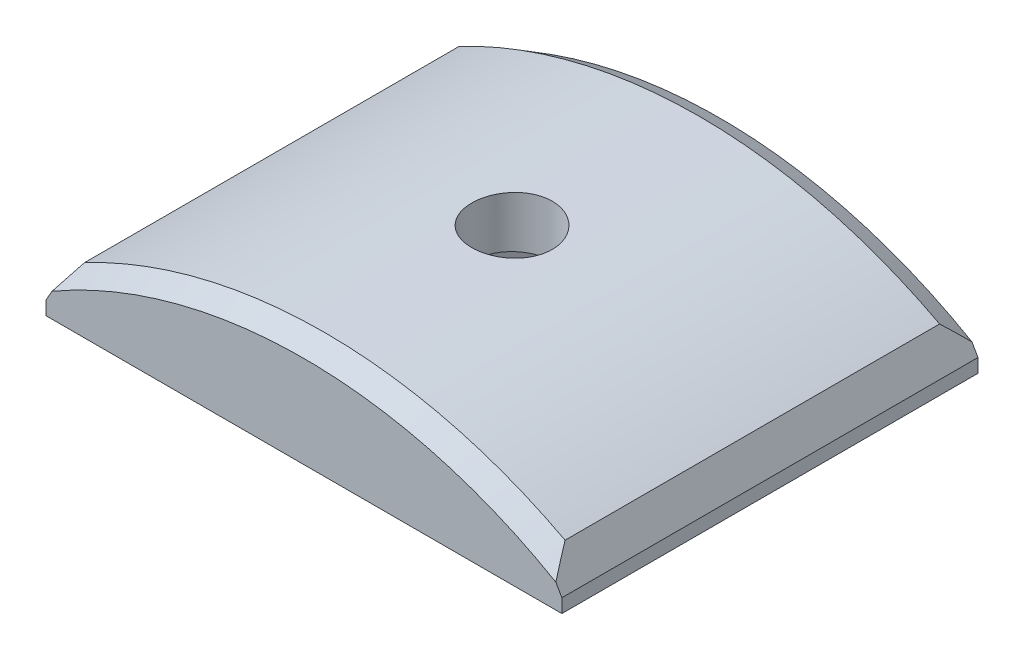
SolidWorks part; units mm, degrees
material "PET"
ref_plane "Front Plane" through (0, 0, 0) normal (0, 0, 1) x (1, 0, 0)
ref_plane "Top Plane" through (0, 0, 0) normal (0, 1, 0) x (1, 0, 0)
ref_plane "Right Plane" through (0, 0, 0) normal (1, 0, 0) x (0, 0, -1)
sketch "Sketch1" plane through (0, 0, 0) normal (0, 0, 1) x (1, 0, 0)
  line L0 (-288.86, -12.7504) -> (-326.6966, -12.7504)
  line L1 (-307.7783, -12.7504) -> (-307.7783, -6.4004) construction
  circle A0 centre (-307.7783, -37.7567) radius 31.3563 construction
  arc A1 (-288.86, -12.7504) -> (-326.6966, -12.7504) centre (-307.7783, -37.7567) ccw
  dimension "D1" = 6.35
extrude "Boss-Extrude1" add sketch "Sketch1" against normal up to surface (25.4 mm away)
sketch "Sketch2" plane through (0, 0, 0) normal (0, 0, 1) x (1, 0, 0)
  line L0 (-292.035, -12.7504) -> (-292.035, -10.6391)
  line L1 (-326.6966, -12.7504) -> (-288.86, -12.7504)
  line L2 (-292.035, -12.7504) -> (-288.86, -12.7504)
  line L3 (-307.7783, -12.7504) -> (-307.7783, -6.4004) construction
  line L4 (-326.6966, -12.7504) -> (-288.86, -12.7504) construction
  line L5 (-323.5216, -12.7504) -> (-326.6966, -12.7504)
  line L6 (-323.5216, -12.7504) -> (-323.5216, -10.6391)
  arc A0 (-288.86, -12.7504) -> (-326.6966, -12.7504) centre (-307.7783, -37.7567) ccw construction
  arc A1 (-288.86, -12.7504) -> (-326.6966, -12.7504) centre (-307.7783, -37.7567) ccw
  arc A2 (-288.86, -12.7504) -> (-292.035, -10.6391) centre (-307.7783, -37.7567) ccw
  arc A3 (-326.6966, -12.7504) -> (-323.5216, -10.6391) centre (-307.7783, -37.7567) cw
  dimension "D2" = 3.175
  dimension "D1" = 0
extrude "Cut-Extrude1" cut sketch "Sketch2" against normal up to next
hole_wizard "#8 Clearance Hole1" positions "Sketch3" profile "Sketch4" hole size "#8" standard "ANSI Inch" end condition through all
sketch "Sketch3" plane through (0, -12.7504, 0) normal (0, -1, 0) x (-1, 0, 0)
  circle A0 centre (307.7783, 12.7) radius 2.4574 construction
  point P0 (307.7783, 12.7)
sketch "Sketch4" plane through (-307.7783, -12.7504, -12.7) normal (1, 0, 0) x (0, 0, -1)
  line L0 (0, 0) -> (0, 6.35)
  line L1 (0, 6.35) -> (2.4574, 6.35)
  line L2 (2.4574, 6.35) -> (2.4574, 0)
  line L5 (2.4574, 0) -> (0, 0)
  line L11 (0, -6.35) -> (0, 107.95) construction
  dimension "Thru Hole Dia." = 4.9149
  dimension "Thru Hole Depth" = 6.35
chamfer "Chamfer1" distance 1.27 angle 30 4 edges at (-292.035, -10.6391, -12.7) (-307.7783, -6.4004, -25.4) (-323.5216, -10.6391, -12.7) (-307.7783, -6.4004, 0)
sketch "Sketch5" plane through (0, -12.7504, 0) normal (0, -1, 0) x (1, 0, 0)
  line L0 (-323.5216, 0) -> (-292.035, 0) construction
  line L1 (-310.418, -17.272) -> (-305.1387, -17.272)
  line L2 (-305.1387, -17.272) -> (-302.499, -12.7)
  line L3 (-302.499, -12.7) -> (-305.1387, -8.128)
  line L4 (-305.1387, -8.128) -> (-310.418, -8.128)
  line L5 (-310.418, -8.128) -> (-313.0576, -12.7)
  line L6 (-313.0576, -12.7) -> (-310.418, -17.272)
  circle A0 centre (-307.7783, -12.7) radius 4.572 construction
  dimension "D1" = 9.144
extrude "Cut-Extrude2" cut sketch "Sketch5" against normal blind 3.175
